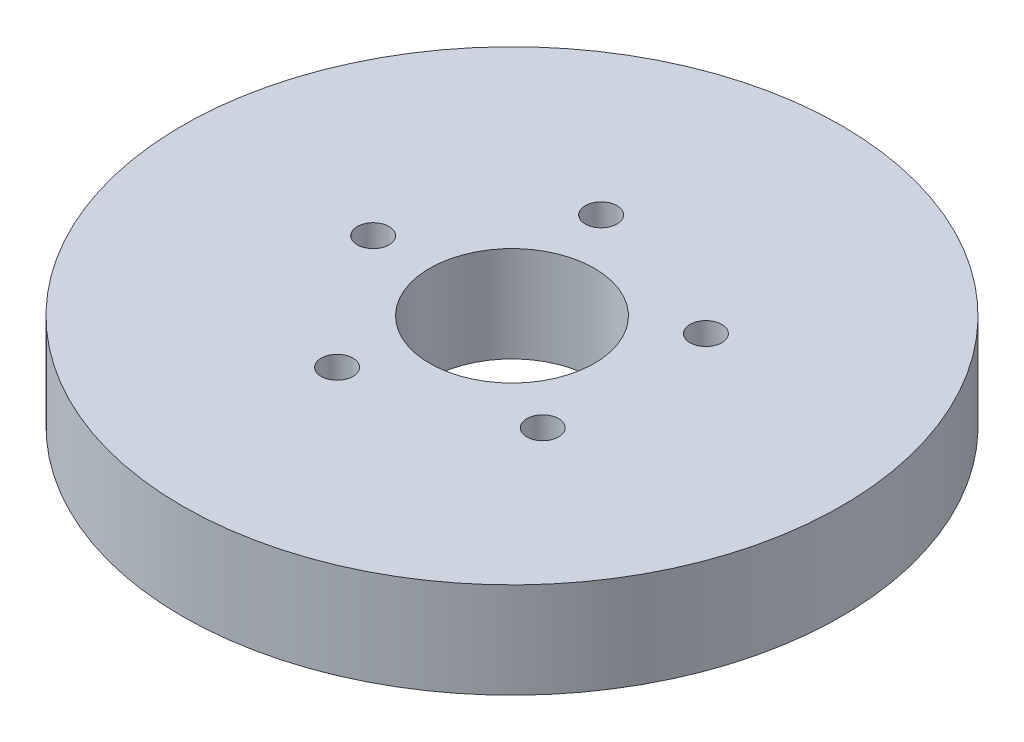
SolidWorks part; units mm, degrees
ref_plane "Front Plane" through (0, 0, 0) normal (0, 0, 1) x (1, 0, 0)
ref_plane "Top Plane" through (0, 0, 0) normal (0, 1, 0) x (1, 0, 0)
ref_plane "Right Plane" through (0, 0, 0) normal (1, 0, 0) x (0, 0, -1)
sketch "Sketch1" plane through (0, 0, 0) normal (0, 1, 0) x (1, 0, 0)
  circle A0 centre (0, 0) radius 100
  dimension "FLANGE_OD" = 200
extrude "Boss-Extrude1" add sketch "Sketch1" along normal blind 29
sketch "Sketch2" plane through (0, 0, 0) normal (0, 1, 0) x (1, 0, 0)
  circle A0 centre (0, 0) radius 25
  dimension "BORE_D" = 50
extrude "Cut-Extrude1" cut sketch "Sketch2" along normal through all
sketch "Sketch3" plane through (0, 29, 0) normal (0, 1, 0) x (1, 0, 0)
  circle A0 centre (0, 0) radius 42.1236 construction
  circle A1 centre (-42.1236, 0) radius 4.8252
  dimension "BOLT_D" = 9.6505
  dimension "BOLT_PCD" = 84.2473
extrude "Cut-Extrude2" cut sketch "Sketch3" against normal blind 17.9013
pattern_circular "CirPattern1" count 5 over 360 about axis through (0, 0, 0) along (0, 1, 0) of "Cut-Extrude2"
